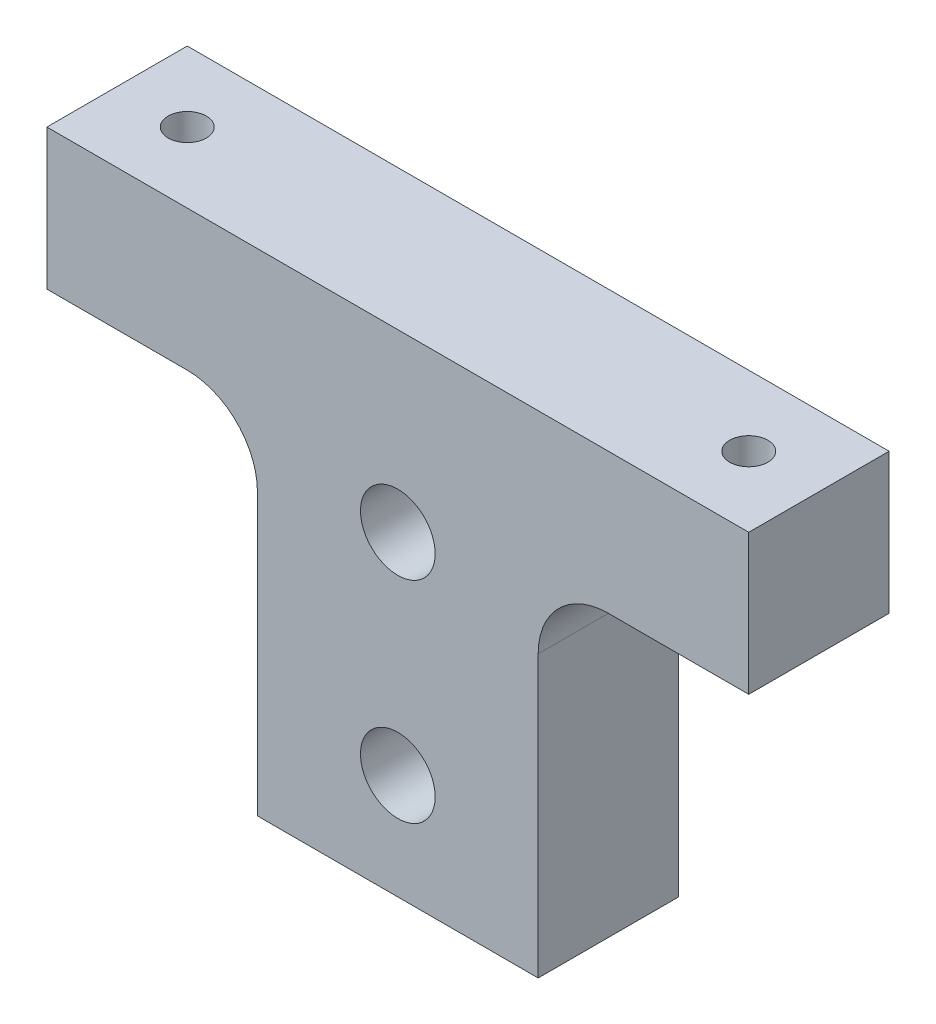
SolidWorks part; units mm, degrees
ref_plane "Front Plane" through (0, 0, 0) normal (0, 0, 1) x (1, 0, 0)
ref_plane "Top Plane" through (0, 0, 0) normal (0, 1, 0) x (1, 0, 0)
ref_plane "Right Plane" through (0, 0, 0) normal (1, 0, 0) x (0, 0, -1)
sketch "Sketch1" plane through (0, 0, 0) normal (0, 0, 1) x (1, 0, 0)
  line L0 (12.7, 15.875) -> (31.75, 15.875)
  line L6 (-12.7, 15.875) -> (-12.7, -15.875)
  line L7 (-12.7, -15.875) -> (12.7, -15.875)
  line L8 (12.7, 15.875) -> (12.7, -15.875)
  line L9 (-12.7, 15.875) -> (12.7, -15.875) construction
  line L10 (-12.7, -15.875) -> (12.7, 15.875) construction
  line L11 (-31.75, 28.575) -> (31.75, 28.575)
  line L12 (-31.75, 28.575) -> (-31.75, 15.875)
  line L13 (-31.75, 15.875) -> (-12.7, 15.875)
  line L14 (31.75, 28.575) -> (31.75, 15.875)
  line L15 (-31.75, 28.575) -> (31.75, 15.875) construction
  line L16 (-31.75, 15.875) -> (31.75, 28.575) construction
  point P0 (0, 0)
  point P6 (0, 22.225)
  dimension "D1" = 12.7
  dimension "D2" = 25.4
  dimension "D3" = 63.5
  dimension "D4" = 31.75
extrude "Boss-Extrude1" add sketch "Sketch1" along normal blind 12.7
fillet "Fillet1" radius 6.35 2 edges at (-12.7, 15.875, 6.35) (12.7, 15.875, 6.35)
hole_wizard "1/4 Clearance Hole1" positions "Sketch2" profile "Sketch3" hole size "1/4" standard "ANSI Inch" end condition through all
sketch "Sketch2" plane through (0, 0, 12.7) normal (0, 0, 1) x (1, 0, 0)
  line L0 (31.75, 28.575) -> (-31.75, 28.575) construction
  line L2 (-12.7, -15.875) -> (12.7, -15.875) construction
  point P0 (0, -6.35)
  point P2 (0, 12.7)
  dimension "D1" = 15.875
  dimension "D2" = 9.525
sketch "Sketch3" plane through (0, -6.35, 12.7) normal (1, 0, 0) x (0, -1, 0)
  line L0 (0, 0) -> (0, 12.7)
  line L1 (0, 12.7) -> (3.3782, 12.7)
  line L2 (3.3782, 12.7) -> (3.3782, 0)
  line L5 (3.3782, 0) -> (0, 0)
  line L11 (0, -6.35) -> (0, 107.95) construction
  dimension "Thru Hole Dia." = 6.7564
  dimension "Thru Hole Depth" = 12.7
hole_wizard "Tap Drill for #8-32 Tap1" positions "Sketch4" profile "Sketch5" hole size "#8-32" standard "ANSI Inch" end condition through all
sketch "Sketch4" plane through (0, 15.875, 0) normal (0, -1, 0) x (-1, 0, 0)
  line L0 (-31.75, -6.35) -> (31.75, -6.35) construction
  line L1 (-31.75, -12.7) -> (-31.75, 0) construction
  line L2 (31.75, -12.7) -> (31.75, 0) construction
  line L4 (-25.4, 0) -> (-25.4, -12.7) construction
  line L8 (25.4, 0) -> (25.4, -12.7) construction
  line L11 (-19.05, -12.7) -> (-31.75, -12.7) construction
  line L12 (31.75, -12.7) -> (19.05, -12.7) construction
  line L13 (31.75, 0) -> (19.05, 0) construction
  point P0 (-25.4, -6.35)
  point P2 (25.4, -6.35)
  point P35 (-25.4, -6.35)
  dimension "D1" = 6.35
  dimension "D2" = 6.35
sketch "Sketch5" plane through (25.4, 15.875, 6.35) normal (1, 0, 0) x (0, 0, -1)
  line L0 (0, 0) -> (0, 12.7)
  line L1 (0, 12.7) -> (1.7272, 12.7)
  line L2 (1.7272, 12.7) -> (1.7272, 0)
  line L5 (1.7272, 0) -> (0, 0)
  line L11 (0, -6.35) -> (0, 107.95) construction
  dimension "Thru Hole Dia." = 3.4544
  dimension "Thru Hole Depth" = 12.7
equation "\"width\"= 2.5"
equation "\"D3@Sketch1\"=\"width\""
